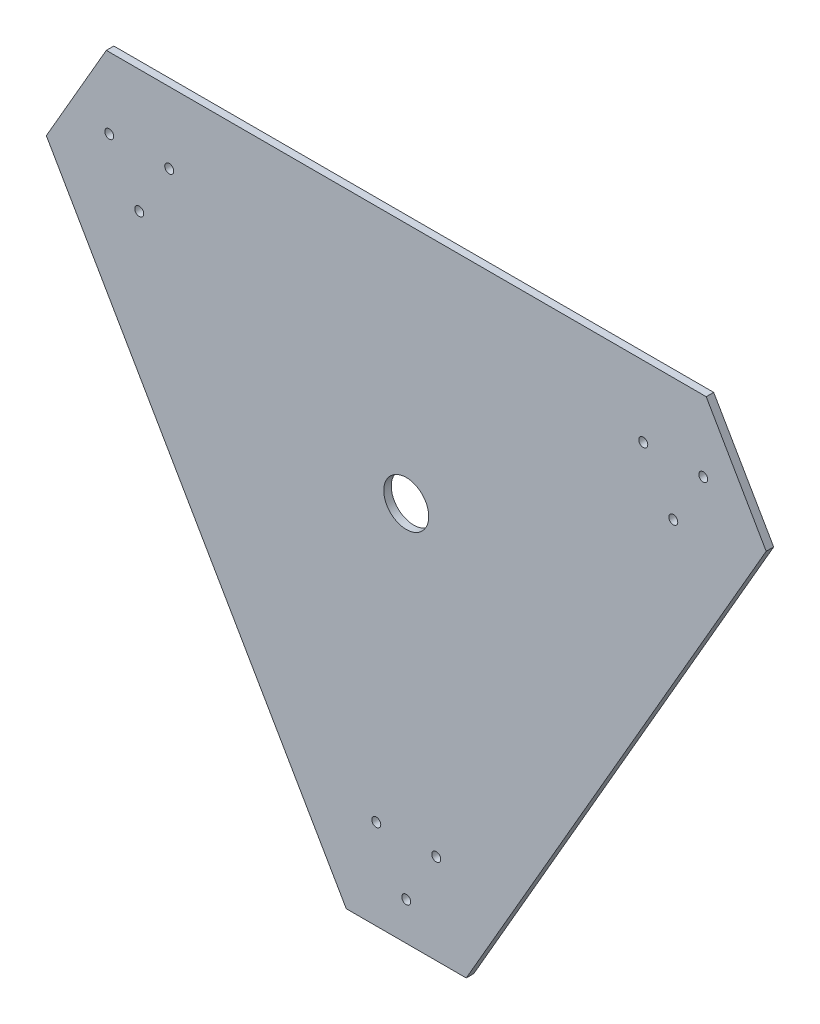
SolidWorks part; units mm, degrees
ref_plane "Спереди" through (0, 0, 0) normal (0, 0, 1) x (1, 0, 0)
ref_plane "Сверху" through (0, 0, 0) normal (0, 1, 0) x (1, 0, 0)
ref_plane "Справа" through (0, 0, 0) normal (1, 0, 0) x (0, 0, -1)
sketch "Эскиз1" plane through (0, 0, 0) normal (0, 0, 1) x (1, 0, 0)
  line L0 (0, 0) -> (20, 34.641)
  line L1 (20, 34.641) -> (220, 34.641)
  line L2 (220, 34.641) -> (240, 0)
  line L3 (240, 0) -> (140, -173.2051)
  line L4 (140, -173.2051) -> (100, -173.2051)
  line L5 (100, -173.2051) -> (0, 0)
  line L7 (30.9812, -6.34) -> (20.9812, 10.9805) construction
  line L8 (20.9812, 10.9805) -> (40.9812, 10.9805) construction
  line L9 (40.9812, 10.9805) -> (30.9812, -6.34) construction
  line L10 (20.9812, 10.9805) -> (10, 17.3205) construction
  line L11 (219.0188, 10.9805) -> (230, 17.3205) construction
  line L12 (209.0188, -6.34) -> (199.0188, 10.9805) construction
  line L13 (199.0188, 10.9805) -> (219.0188, 10.9805) construction
  line L14 (219.0188, 10.9805) -> (209.0188, -6.34) construction
  line L15 (120, -160.5251) -> (110, -143.2046) construction
  line L16 (110, -143.2046) -> (130, -143.2046) construction
  line L17 (130, -143.2046) -> (120, -160.5251) construction
  line L18 (120, -160.5251) -> (120, -173.2051) construction
  line L19 (120, -173.2051) -> (120, 34.641) construction
  line L20 (10, 17.3205) -> (190, -86.6025) construction
  circle A0 centre (20.9812, 10.9805) radius 1.5
  circle A1 centre (40.9812, 10.9805) radius 1.5
  circle A2 centre (30.9812, -6.34) radius 1.5
  circle A3 centre (199.0188, 10.9805) radius 1.5
  circle A4 centre (219.0188, 10.9805) radius 1.5
  circle A5 centre (209.0188, -6.34) radius 1.5
  circle A6 centre (110, -143.2046) radius 1.5
  circle A7 centre (130, -143.2046) radius 1.5
  circle A8 centre (120, -160.5251) radius 1.5
  circle A9 centre (120, -46.188) radius 7.5
  point P27 (120, -46.188)
  dimension "D5" = 3
  dimension "D8" = 15
  dimension "D1" = 40
  dimension "D2" = 60
  dimension "D3" = 60
  dimension "D4" = 200
  dimension "D6" = 12.68
  dimension "D7" = 20
extrude "Бобышка-Вытянуть1" add sketch "Эскиз1" along normal blind 2.5
